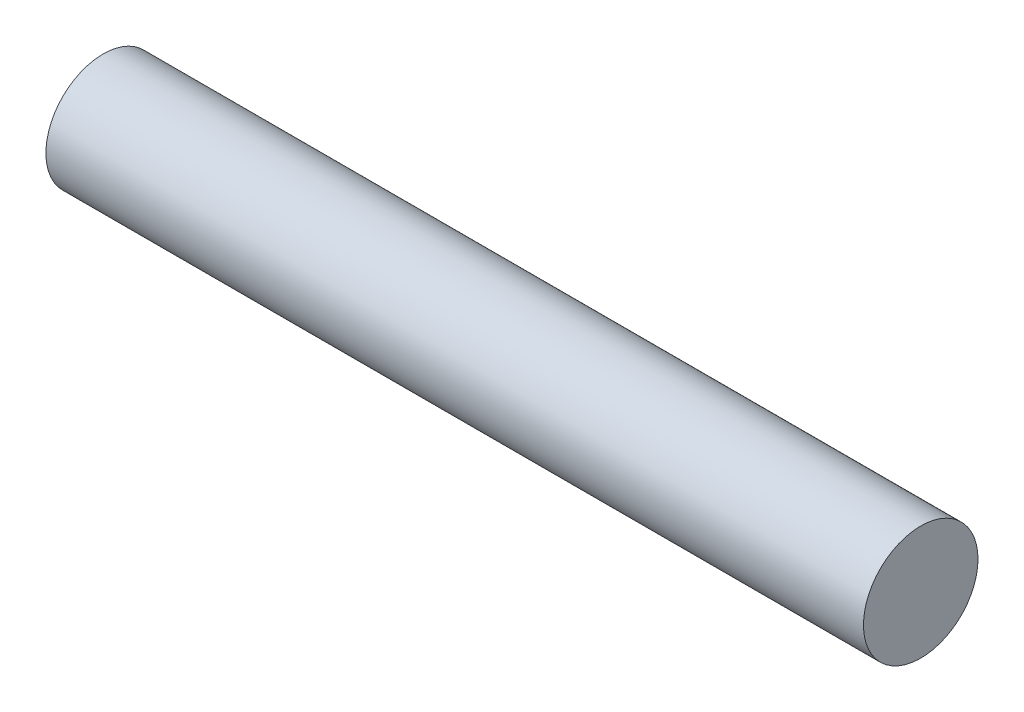
SolidWorks part; units mm, degrees
ref_plane "Front Plane" through (0, 0, 0) normal (0, 0, 1) x (1, 0, 0)
ref_plane "Top Plane" through (0, 0, 0) normal (0, 1, 0) x (1, 0, 0)
ref_plane "Right Plane" through (0, 0, 0) normal (1, 0, 0) x (0, 0, -1)
sketch "Sketch1" plane through (0, 0, 0) normal (1, 0, 0) x (0, 0, -1)
  circle A0 centre (0, 0) radius 22.2928
  dimension "D1" = 44.5856
extrude "Boss-Extrude1" add sketch "Sketch1" against normal blind 318.262
